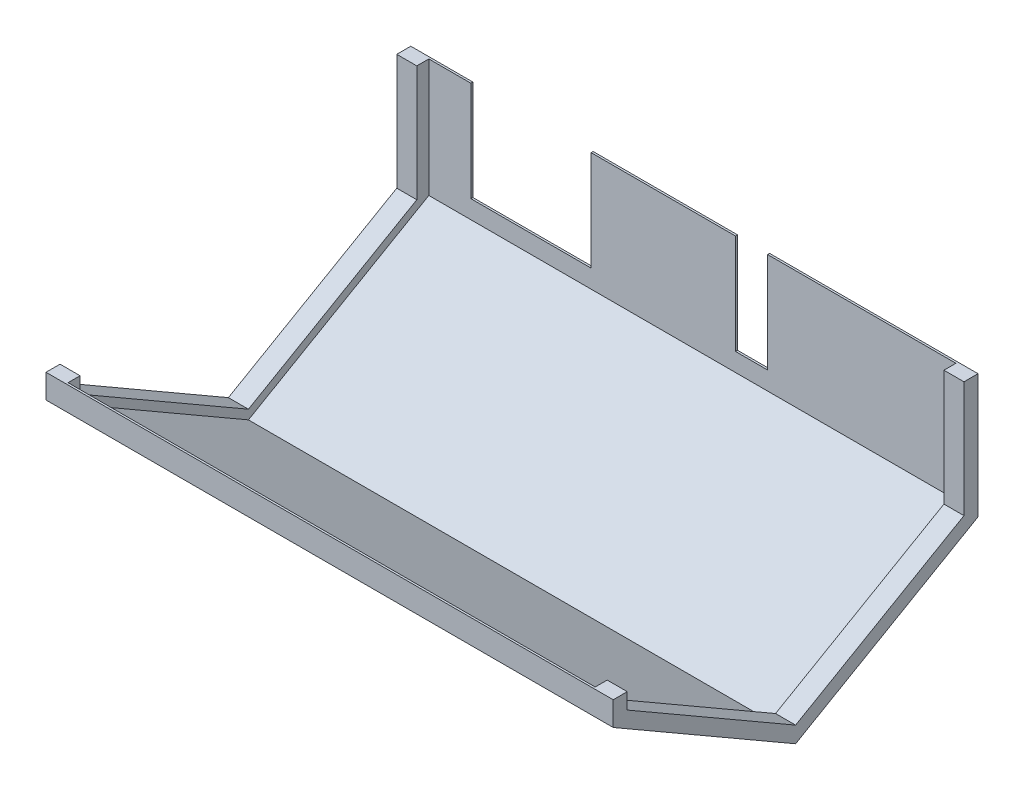
SolidWorks part; units mm, degrees
note: The reader was unsure of these and kept them because the rebuilt part matched: shared geometry of "Эскиз5<2>".
ref_plane "Спереди" through (0, 0, 0) normal (0, 0, 1) x (1, 0, 0)
ref_plane "Сверху" through (0, 0, 0) normal (0, 1, 0) x (1, 0, 0)
ref_plane "Справа" through (0, 0, 0) normal (1, 0, 0) x (0, 0, -1)
other "Configuration Table"
sketch "Эскиз2" plane through (0, 0, 0) normal (1, 0, 0) x (0, 0, -1)
  line L0 (4500, 2750) -> (4500, -2971.2813) construction
  line L1 (9000, 2750) -> (0, 2750) construction
  line L2 (4500, -2971.2813) -> (9050, -344.3376)
  line L3 (9050, -344.3376) -> (9050, 2750)
  line L4 (9050, 2750) -> (9000, 2750)
  line L5 (9000, 2750) -> (9000, -200)
  line L6 (9000, -200) -> (4500, -2798.0762)
  line L7 (9000, -200) -> (9000, 2750) construction
  line L8 (9000, -200) -> (0, -200) construction
  line L9 (0, -200) -> (4500, -2798.0762)
  line L10 (0, 2750) -> (0, -200)
  line L11 (-50, 2750) -> (0, 2750)
  line L12 (-50, -344.3376) -> (-50, 2750)
  line L13 (4500, -2971.2813) -> (-50, -344.3376)
  line L14 (7000, -200) -> (7000, -1354.7005) construction
  dimension "D1" = 150
  dimension "D2" = 50
  dimension "D3" = 5721.2813
  dimension "D4" = 2598.0762
  dimension "D5" = 2500
  dimension "D6" = 1154.7005
  dimension "D7" = 30
extrude "Бобышка-Вытянуть1" add sketch "Эскиз2" against normal up to surface (13150 mm away)
sketch "Эскиз5" plane through (0, 0, 0) normal (1, 0, 0) x (0, 0, -1)
  line L0 (4500, -2971.2813) -> (4500, 3507.5434) construction
  line L1 (-50, 2750) -> (-50, -344.3376)
  line L2 (-50, -344.3376) -> (4500, -2971.2813)
  line L3 (-50, 2750) -> (300, 2750)
  line L4 (300, 2750) -> (300, -142.265)
  line L5 (300, -142.265) -> (4500, -2567.1361)
  line L6 (8700, -142.265) -> (4500, -2567.1361)
  line L7 (8700, 2750) -> (8700, -142.265)
  line L8 (9050, 2750) -> (8700, 2750)
  line L9 (9050, 2750) -> (9050, -344.3376)
  line L10 (9050, -344.3376) -> (4500, -2971.2813)
  dimension "D1" = 350
  dimension "D2" = 350
extrude "Бобышка-Вытянуть2" add sketch "Эскиз5" along normal blind 500
extrude "Бобышка-Вытянуть3" add sketch "Эскиз5<2>" against normal blind 500 from surface at -13150
sketch "Эскиз5<2>" plane through (0, 0, 0) normal (1, 0, 0) x (0, 0, -1) same geometry as "Эскиз5"
sketch "Эскиз4" plane through (0, 0, -9050) normal (0, 0, -1) x (-1, 0, 0)
  line L0 (9000, 3200) -> (9000, 2750) construction
  line L1 (5500, 255.6624) -> (4700, 255.6624)
  line L2 (5500, 255.6624) -> (5500, 3008.1407)
  line L3 (5500, 3008.1407) -> (4700, 3008.1407)
  line L4 (4700, 255.6624) -> (4700, 3008.1407)
  line L5 (9100, 2984.0805) -> (12100, 2984.0805)
  line L6 (9100, 2984.0805) -> (9100, 255.6624)
  line L7 (9100, 255.6624) -> (12100, 255.6624)
  line L8 (12100, 2984.0805) -> (12100, 255.6624)
  line L9 (13650, -344.3376) -> (13650, 2750) construction
  line L10 (13650, -344.3376) -> (-500, -344.3376) construction
  dimension "D1" = 100
  dimension "D2" = 3000
  dimension "D3" = 1550
  dimension "D4" = 600
extrude "Вырез-Вытянуть2" cut sketch "Эскиз4" against normal blind 460
sketch "Эскиз7" plane through (0, 0, 50) normal (0, 0, 1) x (1, 0, 0)
  line L1 (-14440.1641, 3533.1696) -> (1269.69, 3533.1696)
  line L2 (-14440.1641, 3533.1696) -> (-14440.1641, 255.6624)
  line L3 (-14440.1641, 255.6624) -> (1269.69, 255.6624)
  line L4 (1269.69, 3533.1696) -> (1269.69, 255.6624)
  line L5 (-12100, 255.6624) -> (-9100, 255.6624) construction
extrude "Вырез-Вытянуть4" cut sketch "Эскиз7" against normal blind 670
